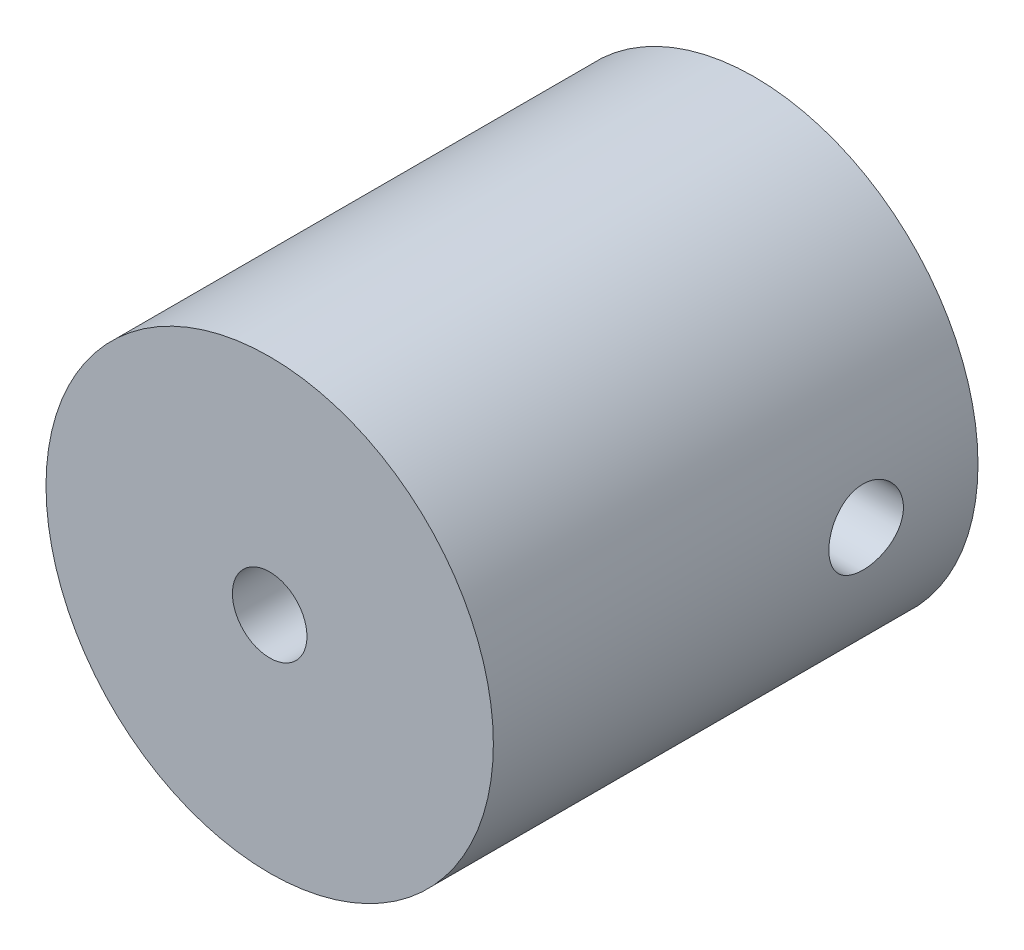
SolidWorks part; units mm, degrees
ref_plane "Front Plane" through (0, 0, 0) normal (0, 0, 1) x (1, 0, 0)
ref_plane "Top Plane" through (0, 0, 0) normal (0, 1, 0) x (1, 0, 0)
ref_plane "Right Plane" through (0, 0, 0) normal (1, 0, 0) x (0, 0, -1)
sketch "Sketch1" plane through (0, 0, 0) normal (0, 0, 1) x (1, 0, 0)
  circle A0 centre (0, 0) radius 15
  circle A1 centre (0, 0) radius 2.5
  dimension "D1" = 30
  dimension "D2" = 5
extrude "Boss-Extrude1" add sketch "Sketch1" along normal blind 32.5
sketch "Sketch2" plane through (0, 0, 0) normal (1, 0, 0) x (0, 0, -1)
  line L0 (0, 0) -> (-7.5, 0) construction
  circle A0 centre (-7.5, 0) radius 2.5
  dimension "D2" = 5
  dimension "D1" = 7.5
extrude "Cut-Extrude1" cut sketch "Sketch2" against normal blind 32.5 and the other way blind 32.5
